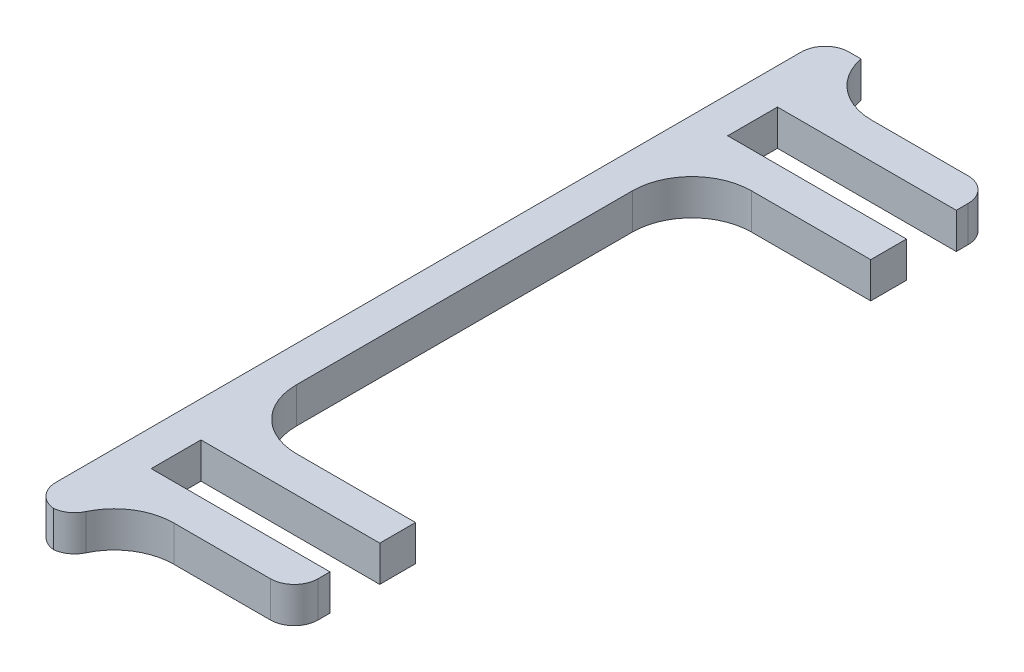
SolidWorks part; units mm, degrees
ref_plane "Front Plane" through (0, 0, 0) normal (0, 0, 1) x (1, 0, 0)
ref_plane "Top Plane" through (0, 0, 0) normal (0, 1, 0) x (1, 0, 0)
ref_plane "Right Plane" through (0, 0, 0) normal (1, 0, 0) x (0, 0, -1)
sketch "Sketch2" plane through (0, 0, 0) normal (0, 1, 0) x (1, 0, 0)
  line L0 (-128.8939, -24.675) -> (-143.8939, -24.675)
  line L1 (-143.8939, 27.865) -> (-143.8939, 23.69)
  line L2 (-143.8939, 27.865) -> (-128.8939, 27.865)
  line L3 (-128.8939, 27.865) -> (-128.8939, 30.865)
  line L4 (-128.8939, 30.865) -> (-143.8939, 30.865)
  line L5 (-143.8939, 23.69) -> (-128.8939, 23.69)
  line L7 (-128.8939, -20.5) -> (-143.8939, -20.5)
  line L8 (-143.8939, -20.5) -> (-143.8939, -24.675)
  line L9 (-128.8939, -24.675) -> (-128.8939, -27.675)
  line L10 (-128.8939, -27.675) -> (-143.8939, -27.675)
  line L11 (-143.8939, -27.675) -> (-143.8939, -31.675)
  line L12 (-143.8939, -31.675) -> (-146.8939, -31.675)
  line L13 (-146.8939, -31.675) -> (-146.8939, 34.865)
  line L14 (-146.8939, 34.865) -> (-143.8939, 34.865)
  line L15 (-143.8939, 34.865) -> (-143.8939, 30.865)
  line L16 (142.8561, 27.365) -> (-142.8939, 27.365) construction
  line L17 (-142.8939, 24.19) -> (142.8561, 24.19) construction
  line L19 (142.3937, -21) -> (-143.3563, -21) construction
  line L21 (-143.3563, -24.175) -> (142.3937, -24.175) construction
  line L22 (-142.8939, 27.365) -> (-142.8939, 24.19) construction
  line L23 (-128.8939, 23.69) -> (-128.8939, 20.69)
  line L24 (-128.8939, 20.69) -> (-143.8939, 20.69)
  line L25 (-143.8939, 20.69) -> (-143.8939, -17.5)
  line L26 (-143.8939, -17.5) -> (-128.8939, -17.5)
  line L27 (-128.8939, -17.5) -> (-128.8939, -20.5)
  point P20 (-136.3939, 27.865)
  point P27 (-147.8573, 31.865)
  point P28 (-146.1974, -28.4393)
  dimension "D1" = 0.5
  dimension "D2" = 0.5
  dimension "D3" = 3
  dimension "D4" = 0.5
  dimension "D5" = 0.5
  dimension "D6" = 1
  dimension "D7" = 15
  dimension "D8" = 3
  dimension "D9" = 3
  dimension "D10" = 3
  dimension "D11" = 3
  dimension "D12" = 4
  dimension "D13" = 4
extrude "Boss-Extrude1" add sketch "Sketch2" along normal blind 3
fillet "Fillet1" radius 5 4 edges at (-143.8939, 1.5, 17.5) (-143.8939, 1.5, -20.69) (-143.8939, 1.5, -30.865) (-143.8939, 1.5, 27.675)
fillet "Fillet2" radius 2 5 edges at (-128.8939, 1.5, 27.675) (-128.8939, 1.5, -30.865) (-143.8939, 1.5, 31.675) (-146.8939, 1.5, -34.865) (-146.8939, 1.5, 31.675)
